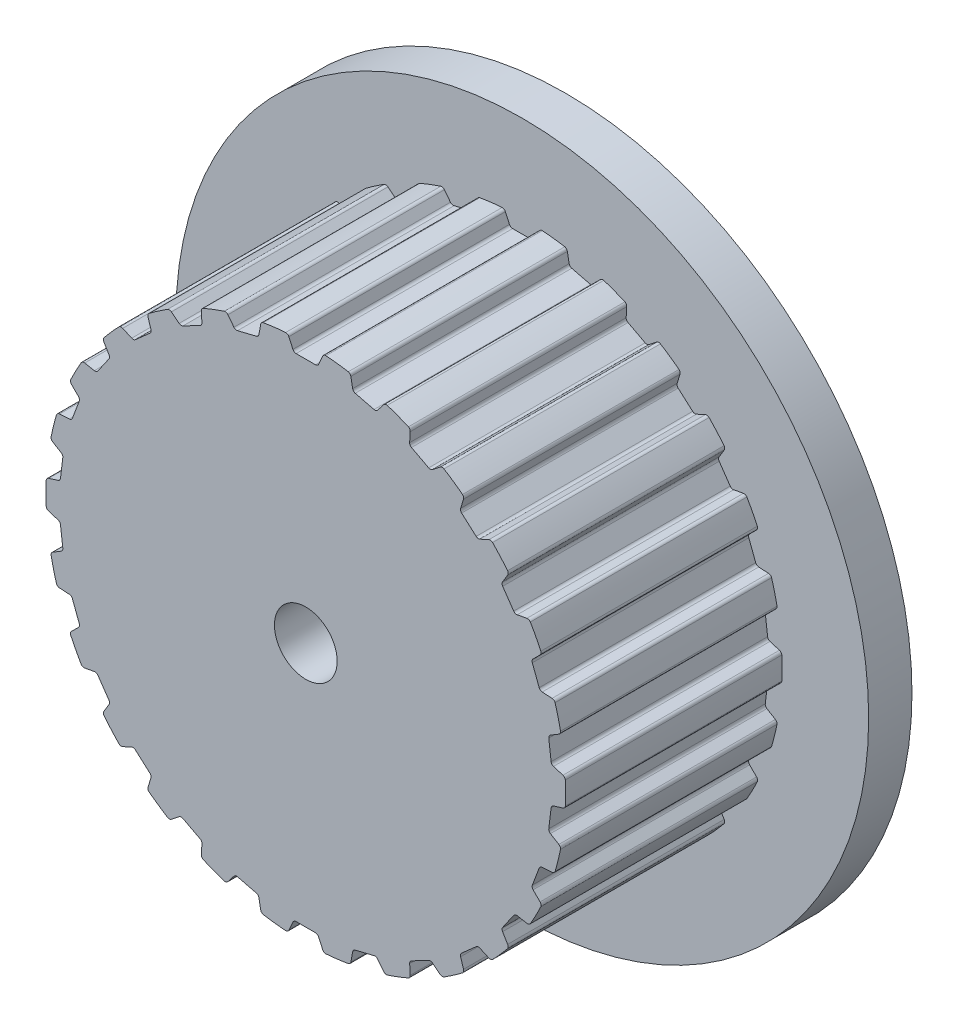
SolidWorks part; units mm, degrees
ref_plane "Front Plane" through (0, 0, 0) normal (0, 0, 1) x (1, 0, 0)
ref_plane "Top Plane" through (0, 0, 0) normal (0, 1, 0) x (1, 0, 0)
ref_plane "Right Plane" through (0, 0, 0) normal (1, 0, 0) x (0, 0, -1)
sketch "Sketch1" plane through (0, 0, 0) normal (0, 0, 1) x (1, 0, 0)
  circle A0 centre (0, 0) radius 12.7
  dimension "D1" = 25.4
extrude "Boss-Extrude1" add sketch "Sketch1" along normal blind 1.5875
sketch "Sketch2" plane through (0, 0, 1.5875) normal (0, 0, 1) x (1, 0, 0)
  circle A0 centre (0, 0) radius 9.525
  dimension "D1" = 19.05
extrude "Boss-Extrude2" add sketch "Sketch2" along normal blind 7.9375
sketch "Sketch3" plane through (0, 0, 9.525) normal (0, 0, 1) x (1, 0, 0)
  circle A0 centre (0, 0) radius 1.15
  dimension "D1" = 2.3
extrude "Cut-Extrude1" cut sketch "Sketch3" against normal through all
sketch "Sketch4" plane through (0, 0, 9.525) normal (0, 0, 1) x (1, 0, 0)
  line L0 (0, 9.017) -> (0, 9.525) construction
  line L1 (-0.3556, 9.017) -> (0.3556, 9.017)
  line L2 (0.4714, 9.0919) -> (0.6198, 9.4217)
  line L3 (-0.7356, 9.4966) -> (0.7356, 9.4966)
  line L4 (-0.4714, 9.0919) -> (-0.6198, 9.4217)
  line L6 (-0.7356, 9.4966) -> (0.7356, 9.4966)
  line L7 (-0.7356, 9.4966) -> (-0.7356, 10.1316)
  line L8 (-0.7356, 10.1316) -> (0.7356, 10.1316)
  line L9 (0.7356, 9.4966) -> (0.7356, 10.1316)
  circle A0 centre (0, 0) radius 9.525 construction
  arc A1 (0.7356, 9.4966) -> (0.6198, 9.4217) centre (0.7356, 9.3696) ccw
  arc A2 (0.3556, 9.017) -> (0.4714, 9.0919) centre (0.3556, 9.144) ccw
  arc A3 (-0.7356, 9.4966) -> (-0.6198, 9.4217) centre (-0.7356, 9.3696) cw
  arc A4 (-0.3556, 9.017) -> (-0.4714, 9.0919) centre (-0.3556, 9.144) cw
  point P13 (0, 9.4966)
  dimension "D1" = 0.127
  dimension "D2" = 0.127
  dimension "D3" = 0.508
  dimension "D4" = 0.635
  dimension "D5" = 0.3616
  dimension "D6" = 0.7112
extrude "Cut-Extrude2" cut sketch "Sketch4" against normal up to surface (7.9375 mm away) contours L3 A1 L2 A2 L1 A4 L4 A3 | L7 L6 L9 L8 up to face at (9.525, 0, 1.5875)
pattern_circular "CirPattern1" count 26 over 360 about axis through (0, 0, 1.5875) along (0, 0, 1) of "Cut-Extrude2"
